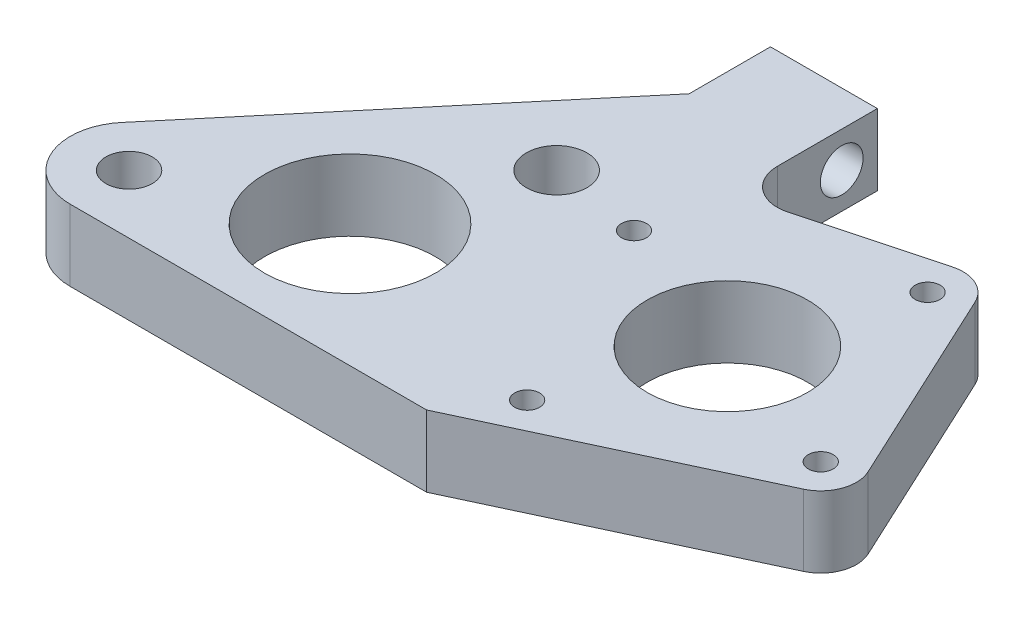
SolidWorks part; units mm, degrees
material "ABS PC"
ref_plane "Спереди" through (0, 0, 0) normal (0, 0, 1) x (1, 0, 0)
ref_plane "Сверху" through (0, 0, 0) normal (0, 1, 0) x (1, 0, 0)
ref_plane "Справа" through (0, 0, 0) normal (1, 0, 0) x (0, 0, -1)
sketch "Sketch1" plane through (0, 0, 0) normal (0, 1, 0) x (1, 0, 0)
  line L0 (42.76, 28.0955) -> (55.8612, 0) construction
  line L1 (55.8612, 0) -> (83.9567, 13.1012) construction
  line L2 (83.9567, 13.1012) -> (70.8555, 41.1967) construction
  line L3 (70.8555, 41.1967) -> (42.76, 28.0955) construction
  line L4 (49.3106, 14.0478) -> (63.3584, 20.5984) construction
  line L5 (63.3584, 20.5984) -> (56.8078, 34.6461) construction
  line L6 (0, -8.25) -> (50, -8.25)
  line L7 (50, -8.25) -> (86.0698, 8.5696)
  line L8 (88.4883, 15.2143) -> (75.3871, 43.3098)
  line L9 (45, 39.4451) -> (69.5615, 46.0263)
  line L10 (30, 48.5873) -> (-6.3199, 5.303)
  line L11 (45, 39.4451) -> (45, 60)
  line L12 (45, 60) -> (30, 60)
  line L13 (30, 60) -> (30, 48.5873)
  circle A0 centre (0, 0) radius 3.25
  circle A1 centre (30, 30) radius 4.25
  circle A2 centre (63.3584, 20.5984) radius 11.25
  circle A3 centre (42.76, 28.0955) radius 1.75
  circle A4 centre (70.8555, 41.1967) radius 1.75
  circle A5 centre (83.9567, 13.1012) radius 1.75
  circle A6 centre (55.8612, 0) radius 1.75
  arc A8 (-6.3199, 5.303) -> (0, -8.25) centre (0, 0) ccw
  circle A9 centre (22, 9) radius 12
  arc A10 (69.5615, 46.0263) -> (75.3871, 43.3098) centre (70.8555, 41.1967) cw
  arc A11 (86.0698, 8.5696) -> (88.4883, 15.2143) centre (83.9567, 13.1012) ccw
  dimension "D1" = 3.5
  dimension "D4" = 8.5
  dimension "D5" = 6.5
  dimension "D7" = 22.5
  dimension "D12" = 5
  dimension "D15" = 24
  dimension "D16" = 22
  dimension "D17" = 9
  dimension "D14" = 50
  dimension "D2" = 30
  dimension "D3" = 30
  dimension "D6" = 31
  dimension "D8" = 5
  dimension "D9" = 15
  dimension "D10" = 65
  dimension "D11" = 50
  dimension "D18" = 30
  dimension "D19" = 100
extrude "Boss-Extrude1" add sketch "Sketch1" along normal blind 10
fillet "Fillet1" radius 5 1 edges at (45, 5, -39.4451)
sketch "Sketch2" plane through (45, 0, 0) normal (1, 0, 0) x (0, 0, -1)
  line L0 (45.9612, 10) -> (60, 10) construction
  line L1 (60, 10) -> (60, 0) construction
  circle A0 centre (55, 5) radius 3
  dimension "D1" = 6
  dimension "D2" = 5
  dimension "D3" = 5
extrude "Cut-Extrude1" cut sketch "Sketch2" against normal up to next
